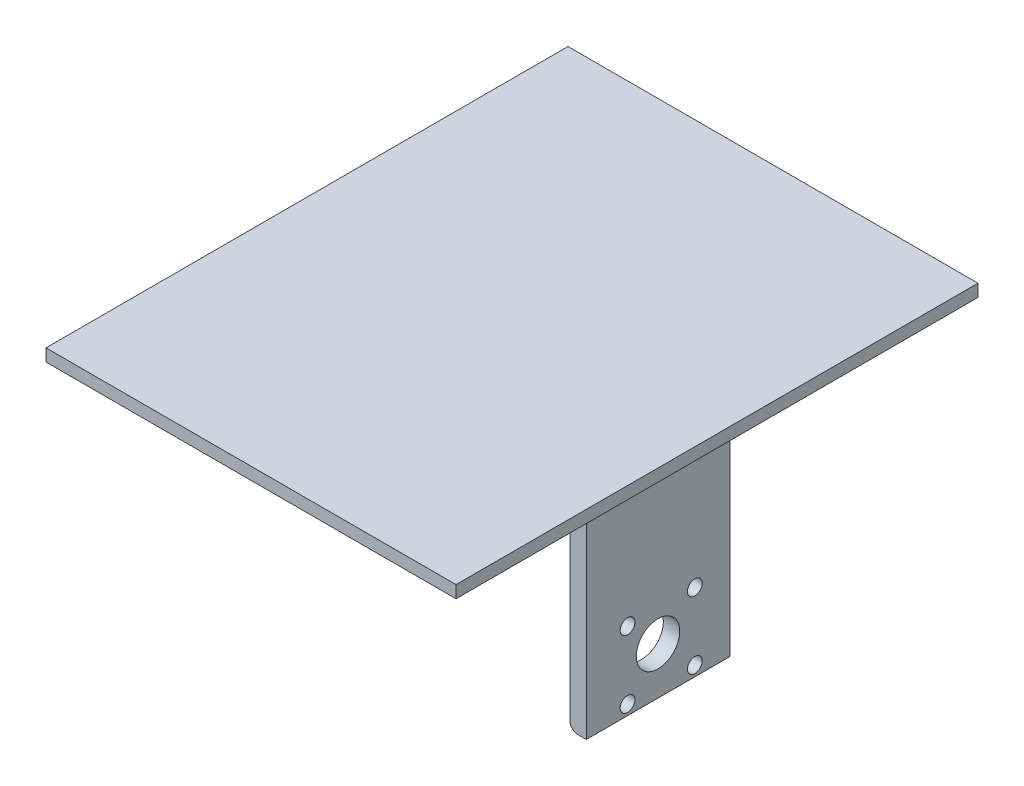
SolidWorks part; units mm, degrees
ref_plane "Alzado" through (0, 0, 0) normal (0, 0, 1) x (1, 0, 0)
ref_plane "Planta" through (0, 0, 0) normal (0, 1, 0) x (1, 0, 0)
ref_plane "Vista lateral" through (0, 0, 0) normal (1, 0, 0) x (0, 0, -1)
sketch "Croquis1" plane through (0, 0, 0) normal (0, 1, 0) x (1, 0, 0)
  line L1 (-50, 63.6524) -> (50, 63.6524)
  line L2 (-50, 63.6524) -> (-50, -63.6524)
  line L3 (-50, -63.6524) -> (50, -63.6524)
  line L4 (50, 63.6524) -> (50, -63.6524)
  line L5 (-50, 63.6524) -> (50, -63.6524) construction
  line L6 (-50, -63.6524) -> (50, 63.6524) construction
  point P0 (0, 0)
  dimension "D1" = 100
extrude "Saliente-Extruir1" add sketch "Croquis1" along normal blind 3
sketch "Croquis2" plane through (0, 0, 0) normal (0, -1, 0) x (1, 0, 0)
  line L0 (50, 0) -> (-50, 0) construction
  line L1 (35.6108, 17.4962) -> (31.6108, 17.4962)
  line L2 (35.6108, 17.4962) -> (35.6108, -17.4962)
  line L3 (35.6108, -17.4962) -> (31.6108, -17.4962)
  line L4 (31.6108, 17.4962) -> (31.6108, -17.4962)
  line L5 (50, 63.6524) -> (50, -63.6524) construction
  line L6 (-50, -63.6524) -> (-50, 63.6524) construction
  point P10 (35.6108, 0)
  dimension "D1" = 4
extrude "Saliente-Extruir2" add sketch "Croquis2" along normal blind 60
sketch "Croquis3" plane through (35.6108, 0, 0) normal (1, 0, 0) x (0, 0, -1)
  line L0 (0, -38.0249) -> (0, -48.5249) construction
  line L1 (0, -48.5249) -> (-7.4246, -41.1002) construction
  line L2 (0, 0) -> (0, -60) construction
  line L3 (17.4962, -60) -> (-17.4962, -60) construction
  circle A0 centre (0, -48.5249) radius 5.3
  circle A1 centre (0, -48.5249) radius 10.5 construction
  circle A2 centre (-7.4246, -41.1002) radius 1.8
  circle A3 centre (8.981, -41.1002) radius 1.8
  circle A4 centre (8.981, -57.5059) radius 1.8
  circle A5 centre (-7.4246, -57.5059) radius 1.8
  point P20 (0.7782, -49.3031)
  dimension "D2" = 21
  dimension "D3" = 10.6
  dimension "D4" = 3.6
  dimension "D1" = 45
  dimension "D5" = 4
extrude "Cortar-Extruir1" cut sketch "Croquis3" against normal blind 10
chamfer "Chaflán1" distance 10 angle 45 1 edges at (31.6108, 0, 0)
fillet "Redondeo1" radius 2 1 edges at (31.6108, -60, 0)
